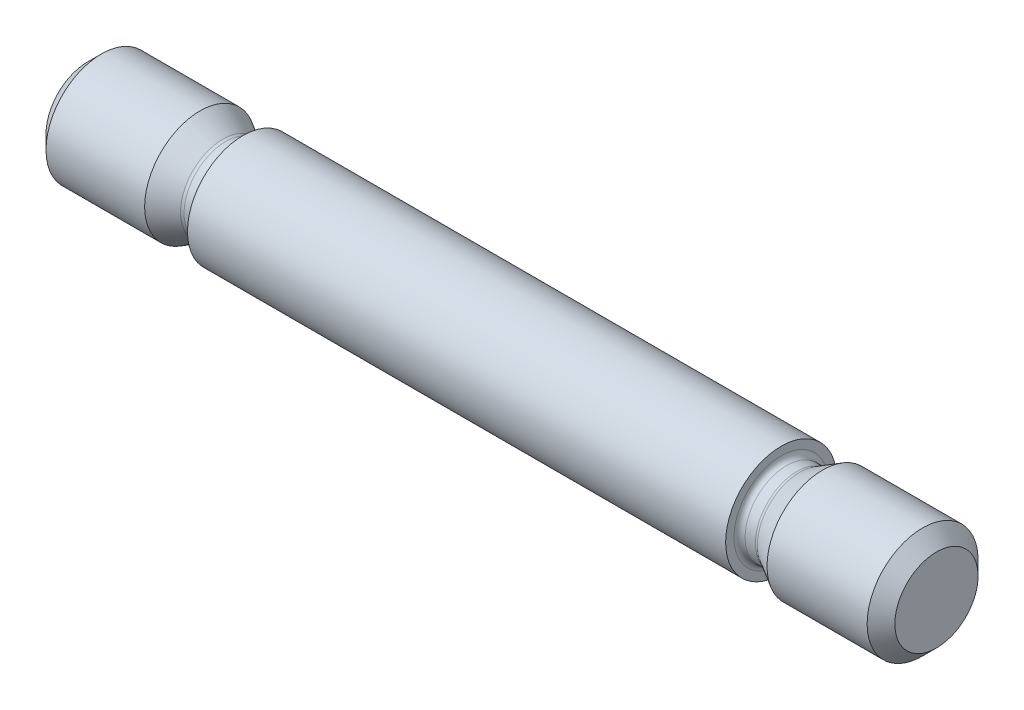
SolidWorks part; units mm, degrees
revolve "BaseBody" add sketch "BodySke" angle 360 about L14 other way angle 60
sketch "BodySke" plane through (0, 0, 0) normal (0, 0, 1) x (1, 0, 0)
  line L0 (19.5, 6.1072) -> (16.2215, 8)
  line L1 (16.2215, 8) -> (2, 8)
  line L2 (22.4, 8) -> (22.4, 6.8)
  line L3 (21.6, 6) -> (19.9, 6)
  line L5 (2, 8) -> (0, 6)
  line L7 (100, 8) -> (100, 6.8)
  line L8 (100.8, 6) -> (102.2856, 6)
  line L9 (102.6856, 6.1072) -> (105.9641, 8)
  line L10 (105.9641, 8) -> (120.4, 8)
  line L11 (120.4, 8) -> (122.4, 6)
  line L12 (122.4, 6) -> (122.4, 0)
  line L13 (122.4, 0) -> (0, 0)
  line L14 (-3.175, 0) -> (101.6, 0) construction
  line L15 (108.7794, -6) -> (122.4, -6) construction
  line L16 (100, -6) -> (102.5, -6) construction
  line L17 (37.0699, -8) -> (100, -8) construction
  line L18 (0, 6) -> (0, 0)
  line L19 (22.4, 8) -> (100, 8)
  line L20 (104.5, 10.8514) -> (104.5, -6.5014) construction
  line L21 (100, 10.2761) -> (100, -5.5735) construction
  arc A0 (19.9, 6) -> (19.5, 6.1072) centre (19.9, 6.8) cw
  arc A1 (22.4, 6.8) -> (21.6, 6) centre (21.6, 6.8) cw
  arc A2 (102.2856, 6) -> (102.6856, 6.1072) centre (102.2856, 6.8) ccw
  arc A3 (100, 6.8) -> (100.8, 6) centre (100.8, 6.8) ccw
  point P26 (102.5, 6)
  point P29 (100, 6)
  dimension "Advance" = 2
  dimension "Shoulder_neck_width" = 2.5
  dimension "Length" = 100
  dimension "Thread_len" = 22.4
cosmetic thread "ThreadCosmetic" [suppressed] parameters "Thread_minor"=12
cosmetic thread "ThreadCosmeticStud" [suppressed] parameters "Thrd_Minor"=12
ref_plane "Plane1" through (0, 0, 0) normal (0, 0, 1) x (1, 0, 0)
ref_plane "Plane2" through (0, 0, 0) normal (0, 1, 0) x (1, 0, 0)
ref_plane "Plane3" through (0, 0, 0) normal (1, 0, 0) x (0, 0, -1)
sketch "ThdSchSke" plane through (0, 0, 0) normal (0, 0, 1) x (1, 0, 0)
  line L0 (104.5, -6) -> (103.0996, -8)
  line L1 (104.5, -6) -> (105.9004, -8)
  line L2 (105.9004, -8) -> (105.9004, -10)
  line L3 (-3.175, 0) -> (5.1513, 0) construction
  line L5 (105.9004, -10) -> (103.0996, -10)
  line L6 (103.0996, -10) -> (103.0996, -8)
  line L7 (122.4, -6) -> (122.4, 6) construction
  dimension "Thread_minor" = 12
  dimension "Diameter" = 16
  dimension "Start" = 17.9
  dimension "SideAngle" = 55
  dimension "VeeAngle" = 70
  dimension "Overcut" = 20
revolve "ThreadSchematic" [suppressed] cut sketch "ThdSchSke" angle 360 about L3
pattern_linear "ThdSchPat" [suppressed]
sketch "ThdSchSketStud" plane through (0, 0, 0) normal (0, 0, 1) x (1, 0, 0)
  line L0 (17.9, -6) -> (16.4996, -8)
  line L1 (17.9, -6) -> (19.3004, -8)
  line L2 (19.3004, -8) -> (19.3004, -10)
  line L3 (-3.175, 0) -> (5.1513, 0) construction
  line L5 (19.3004, -10) -> (16.4996, -10)
  line L6 (16.4996, -10) -> (16.4996, -8)
  line L7 (0, 6) -> (0, -6) construction
  dimension "Thread_minor" = 12
  dimension "Diameter" = 16
  dimension "SideAngle" = 55
  dimension "VeeAngle" = 70
  dimension "Overcut" = 20
revolve "ThreadSchematicStud" [suppressed] cut sketch "ThdSchSketStud" angle 360 about L3
pattern_linear "ThdSchPatStud" [suppressed]
equation "\"Thread_len@BodySke\" = \"Thread_nom@BodySke\""
equation "\"Studend_length@BodySke\" = \"Thread_len@BodySke\""
equation "\"Thread_minor@ThreadCosmetic\" = \"Minor_dia@BodySke\""
equation "\"Thrd_Minor@ThreadCosmeticStud\" = \"Thread_minor@ThreadCosmetic\""
equation "\"Thread_minor@ThdSchSke\" = \"Minor_dia@BodySke\""
equation "\"Diameter@ThdSchSke\" = \"Thread_dia@BodySke\""
equation "\"Overcut@ThdSchSke\" = \"Thread_dia@BodySke\" * 1.25"
equation "\"Start@ThdSchSke\" = \"Thread_nom@BodySke\"  - \"Thread_neck_width@BodySke\" - \"Advance@BodySke\""
equation "\"Num_threads@ThdSchPat\" = int( \"Start@ThdSchSke\" / \"Advance@BodySke\" + 0.999 ) + 1"
equation "\"Advance@ThdSchPat\" = \"Start@ThdSchSke\" /  ( \"Num_threads@ThdSchPat\" - 1 ) 'relax it"
equation "'  \"Num_threads@ThdSchPat\" = \"Num_threads@ThdSchPat\" - sgn( \"Num_threads@ThdSchPat\" - 1 ) '---chamfered tips only---"
equation "\"Diameter@ThdSchSketStud\" = \"Diameter@ThdSchSke\""
equation "\"Thread_minor@ThdSchSketStud\" = \"Thread_minor@ThdSchSke\""
equation "\"Overcut@ThdSchSketStud\" = \"Overcut@ThdSchSke\""
equation "\"Start_@ThdSchSketStud\" = \"Studend_length@BodySke\" - \"Shoulder_neck_width@BodySke\" - \"Advance@BodySke\""
equation "\"Num_Threads@ThdSchPatStud\" = int ( \"Start_@ThdSchSketStud\" / \"Advance@BodySke\" + 0.999 )  + 1"
equation "\"Advance@ThdSchPatStud\" = \"Start_@ThdSchSketStud\" /  ( \"Num_Threads@ThdSchPatStud\" - 1 ) 'relax it"
